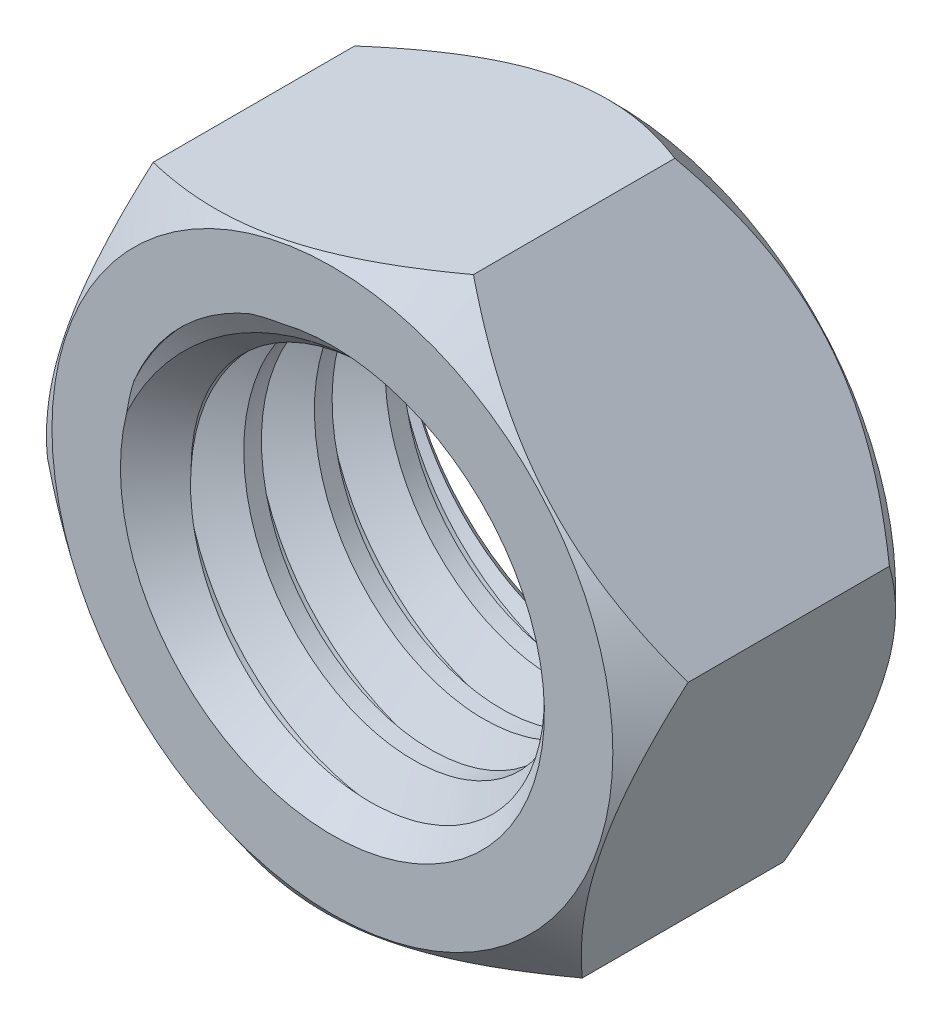
SolidWorks part; units mm, degrees
ref_plane "Plano frontal" through (0, 0, 0) normal (0, 0, 1) x (1, 0, 0)
ref_plane "Plano superior" through (0, 0, 0) normal (0, 1, 0) x (1, 0, 0)
ref_plane "Plano direito" through (0, 0, 0) normal (1, 0, 0) x (0, 0, -1)
sketch "Esboço1" plane through (0, 0, 0) normal (0, 0, 1) x (1, 0, 0)
  line L1 (3.0366, -3.4803) -> (4.5323, 0.8897)
  line L2 (4.5323, 0.8897) -> (1.4957, 4.3699)
  line L3 (1.4957, 4.3699) -> (-3.0366, 3.4803)
  line L4 (-3.0366, 3.4803) -> (-4.5323, -0.8897)
  line L5 (-4.5323, -0.8897) -> (-1.4957, -4.3699)
  line L6 (-1.4957, -4.3699) -> (3.0366, -3.4803)
  circle A0 centre (0, 0) radius 4 construction
  dimension "D1" = 8
extrude "Ressalto-extrusão1" add sketch "Esboço1" along normal blind 4
hole_wizard "Furo roscado de M61" positions "Esboço2" profile "Esboço3" tap size "M6" standard "ISO" end condition up to next
sketch "Esboço2" plane through (0, 0, 4) normal (0, 0, 1) x (1, 0, 0)
  point P0 (0, 0)
sketch "Esboço3" plane through (0, 0, 4) normal (1, 0, 0) x (0, -1, 0)
  line L0 (0, 0) -> (0, 4)
  line L1 (0, 4) -> (2.5, 4)
  line L2 (2.5, 4) -> (2.5, 0)
  line L5 (2.5, 0) -> (0, 0)
  line L11 (0, -6.35) -> (0, 107.95) construction
  dimension "Thru Tap Drill Dia." = 5
  dimension "Thru Tap Drill Depth" = 4
cosmetic thread "Rosca de furo1" parameters "D2"=6
chamfer "Chanfro1" distance 0.5 angle 45 2 edges at (2.5, 0, 0) (2.5, 0, 4)
thread "Rosca1" pitch 1 method cut profile "Perfil da rosca1" start angle 0, offset 1, length 0, pitch 1, diameter 5
ref_plane "Plano1" through (-2.5, 0, 4.5) normal (0, -1, 0) x (-1, 0, 0)
sketch "Perfil da rosca1" plane through (-2.5, 0, 4.5) normal (0, -1, 0) x (-1, 0, 0)
  line L0 (0, 0) -> (0, 1) construction
  line L1 (0, 0) -> (0.5413, 0.3125)
  line L2 (0.5413, 0.3125) -> (0.5413, 0.4375)
  line L3 (0.5413, 0.4375) -> (0, 0.75)
  line L4 (0.5413, 0.375) -> (0, 0.375) construction
  line L11 (0, 0) -> (0, 0.75)
  point P2 (0, 0)
  dimension "Pitch" = 1
  dimension "Profile_Angle" = 60
  dimension "Profile_Land" = 0.125
  dimension "Profile_Height" = 0.5413
ref_plane "Plano2" through (0, 0, 0) normal (0.9461, -0.3238, 0) x (0, 0, -1)
sketch "Esboço11" plane through (0, 0, 0) normal (0.9461, -0.3238, 0) x (0, 0, -1)
  line L0 (-4, 4.6188) -> (-4, 3.9688)
  line L1 (-4, 2.3094) -> (-4, 4.6188) construction
  line L2 (-4, 3.9688) -> (-3.5, 4.6188)
  line L3 (-4, 4.6188) -> (0, 4.6188) construction
  line L4 (-3.5, 4.6188) -> (-4, 4.6188)
  line L5 (0, 0) -> (-5.4718, 0) construction
  dimension "D1" = 0.5
  dimension "D2" = 0.65
revolve "Corte-Revolução1" cut sketch "Esboço11" angle 360 about L5
sketch "Esboço13" plane through (0, 0, 0) normal (0.9461, -0.3238, 0) x (0, 0, -1)
  line L0 (0, 4.6188) -> (0, 3.9688)
  line L1 (0, 2.3094) -> (0, 4.6188) construction
  line L2 (0, 3.9688) -> (-0.65, 4.6188)
  line L3 (-3.5, 4.6188) -> (0, 4.6188) construction
  line L4 (-0.65, 4.6188) -> (0, 4.6188)
  dimension "D1" = 0.65
  dimension "D2" = 0.65
revolve "Corte-Revolução2" cut sketch "Esboço13" angle 360 about axis through (0, 0, 4) along (0, 0, 1)
